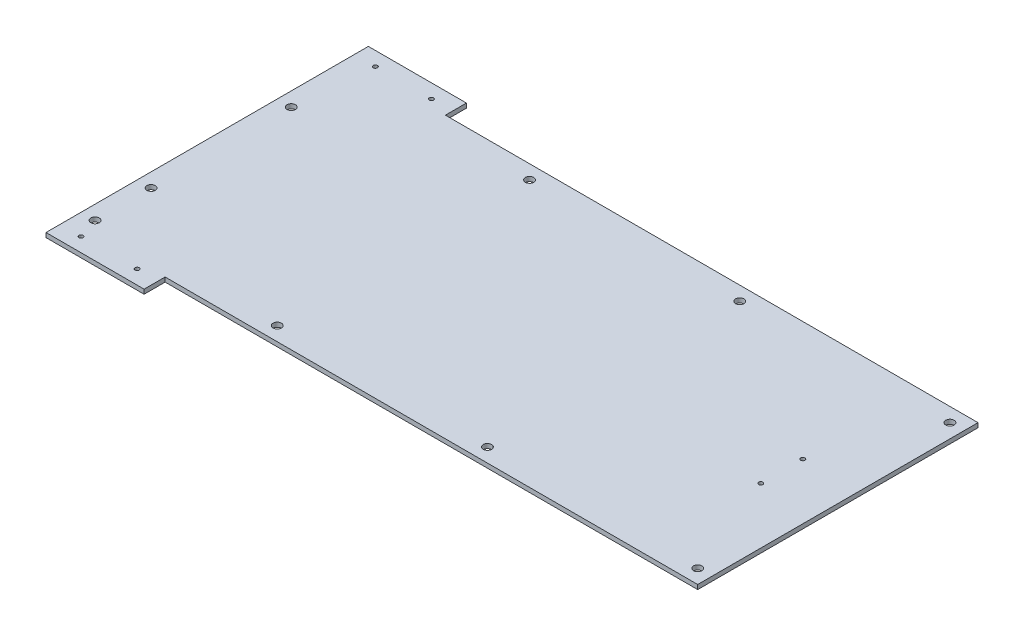
SolidWorks part; units mm, degrees
ref_plane "Front Plane" through (0, 0, 0) normal (0, 0, 1) x (1, 0, 0)
ref_plane "Top Plane" through (0, 0, 0) normal (0, 1, 0) x (1, 0, 0)
ref_plane "Right Plane" through (0, 0, 0) normal (1, 0, 0) x (0, 0, -1)
sketch "Sketch1" plane through (0, 0, 0) normal (0, 1, 0) x (1, 0, 0)
  line L1 (70, 110.4681) -> (450, 110.4681)
  line L3 (70, 310.4681) -> (450, 310.4681)
  line L4 (450, 110.4681) -> (450, 310.4681)
  line L5 (0, 325.4681) -> (70, 325.4681)
  line L6 (70, 325.4681) -> (70, 310.4681)
  line L8 (0, 95.4681) -> (70, 95.4681)
  line L9 (70, 95.4681) -> (70, 110.4681)
  line L10 (35, 325.4681) -> (35, 95.4681) construction
  line L12 (0, 95.4681) -> (0, 325.4681)
  line L13 (0, 210.4681) -> (449.8782, 210.4681) construction
  circle A0 centre (55, 315.4681) radius 1.5
  circle A1 centre (15, 315.4681) radius 1.5
  circle A2 centre (55, 105.4681) radius 1.5
  circle A3 centre (15, 105.4681) radius 1.5
  circle A4 centre (410, 225.4681) radius 1.5
  circle A5 centre (410, 195.4681) radius 1.5
  circle A7 centre (10, 260.4681) radius 3
  circle A9 centre (440, 300.4681) radius 3
  circle A10 centre (140, 300.4681) radius 3
  circle A12 centre (290, 300.4681) radius 3
  circle A15 centre (440, 120.4681) radius 3
  circle A16 centre (290, 120.4681) radius 3
  circle A18 centre (140, 120.4681) radius 3
  circle A19 centre (10, 120.4681) radius 3
  circle A20 centre (10, 160.4681) radius 3
  point P12 (15, 105.4681)
  point P17 (55, 105.4681)
  dimension "D6" = 20
  dimension "D8" = 15
  dimension "D10" = 3
  dimension "D16" = 10
  dimension "D17" = 10
  dimension "D20" = 150
  dimension "D26" = 6
  dimension "D28" = 6
  dimension "D30" = 6
  dimension "D31" = 6
  dimension "D1" = 15
  dimension "D2" = 70
  dimension "D3" = 70
  dimension "D4" = 15
  dimension "D5" = 200
  dimension "D7" = 20
  dimension "D9" = 15
  dimension "D11" = 40
  dimension "D12" = 40
  dimension "D13" = 450
  dimension "D14" = 5
  dimension "D15" = 5
  dimension "D18" = 10
  dimension "D19" = 50
extrude "Boss-Extrude1" add sketch "Sketch1" along normal blind 3.175
